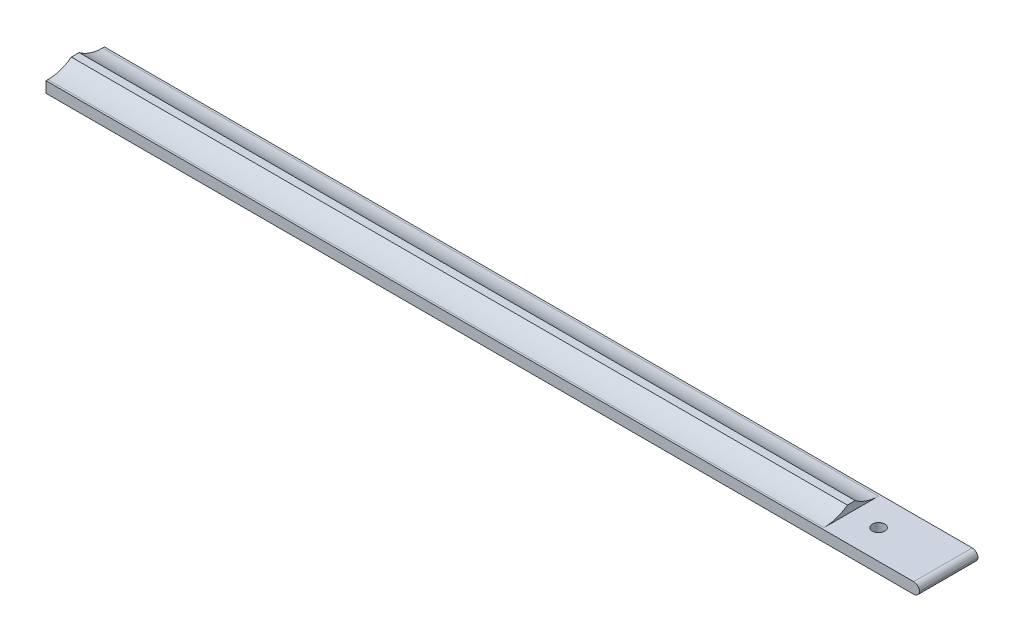
SolidWorks part; units mm, degrees
ref_plane "Front Plane" through (0, 0, 0) normal (0, 0, 1) x (1, 0, 0)
ref_plane "Top Plane" through (0, 0, 0) normal (0, 1, 0) x (1, 0, 0)
ref_plane "Right Plane" through (0, 0, 0) normal (1, 0, 0) x (0, 0, -1)
sketch "Sketch1" plane through (0, 0, 0) normal (0, 1, 0) x (1, 0, 0)
  line L1 (-112, 7.5) -> (112, 7.5)
  line L2 (-112, 7.5) -> (-112, -7.5)
  line L3 (-112, -7.5) -> (112, -7.5)
  line L4 (112, 7.5) -> (112, -7.5)
  line L5 (-112, 7.5) -> (112, -7.5) construction
  line L6 (-112, -7.5) -> (112, 7.5) construction
  point P0 (0, 0)
  dimension "D1" = 224
  dimension "D2" = 15
extrude "Boss-Extrude1" add sketch "Sketch1" along normal blind 2.8
sketch "Sketch2" plane through (0, 2.8, 0) normal (0, 1, 0) x (1, 0, 0)
  line L0 (-112, 7.5) -> (-112, -7.5) construction
  line L1 (-112, 1) -> (87, 1)
  line L2 (-112, 1) -> (-112, -1)
  line L3 (-112, -1) -> (87, -1)
  line L4 (87, 1) -> (87, -1)
  line L5 (112, 7.5) -> (-112, 7.5) construction
  line L6 (112, -7.5) -> (112, 7.5) construction
  dimension "D1" = 2
  dimension "D2" = 6.5
  dimension "D3" = 25
extrude "Boss-Extrude2" add sketch "Sketch2" along normal blind 2
sketch "Sketch3" plane through (0, 2.8, 0) normal (0, 1, 0) x (1, 0, 0)
  line L0 (87, -1) -> (87, 1) construction
  line L2 (-112, -1) -> (87, -1) construction
  circle A0 centre (94, 0) radius 1.6
  dimension "D1" = 3.2
  dimension "D2" = 7
  dimension "D3" = 1
extrude "Cut-Extrude1" cut sketch "Sketch3" against normal through all
fillet "Fillet1" radius 10 2 edges at (-12.5, 2.8, -1) (-12.5, 2.8, 1)
fillet "Fillet2" radius 1.5 2 edges at (112, 0, 0) (112, 2.8, 0)
